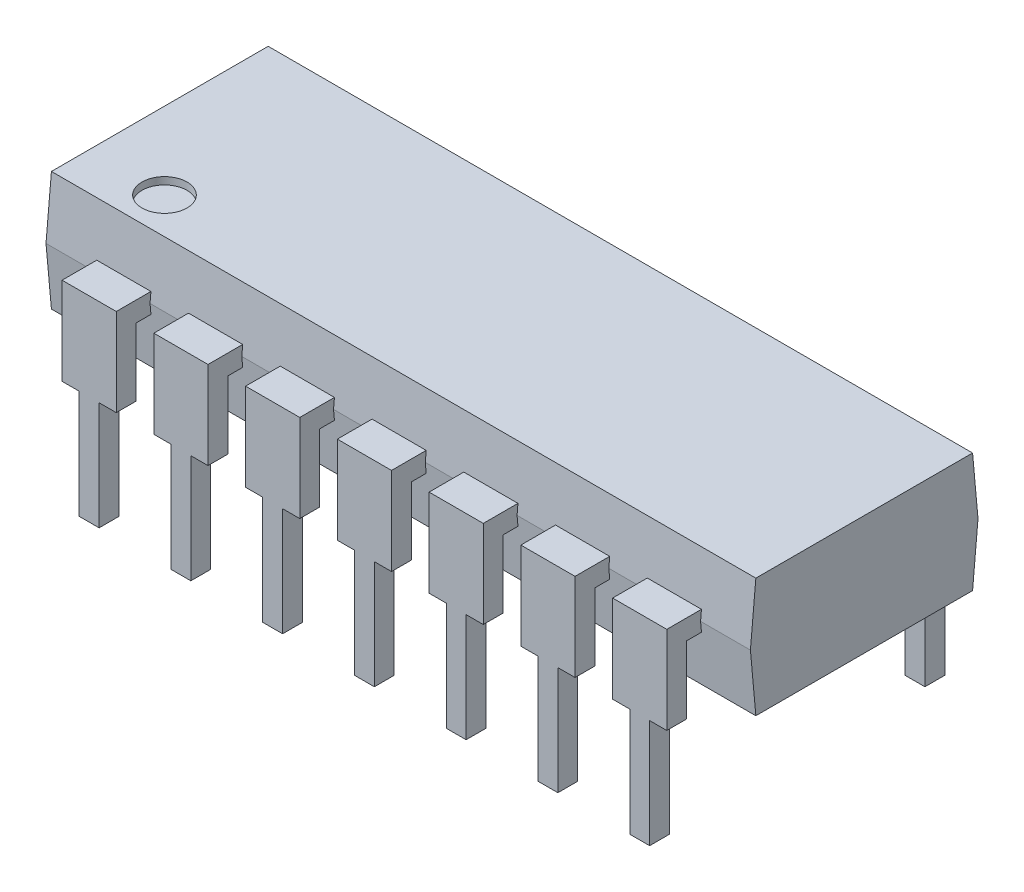
SolidWorks part; units mm, degrees
ref_plane "Front Plane" through (0, 0, 0) normal (0, 0, 1) x (1, 0, 0)
ref_plane "Top Plane" through (0, 0, 0) normal (0, 1, 0) x (1, 0, 0)
ref_plane "Right Plane" through (0, 0, 0) normal (1, 0, 0) x (0, 0, -1)
sketch "Sketch2" plane through (0, 0, 0) normal (1, 0, 0) x (0, 0, -1)
  line L0 (0, 0) -> (0, 3.3)
  line L1 (0, 3.3) -> (-3, 3.3)
  line L2 (-3, 3.3) -> (-3.15, 1.65)
  line L3 (-3.15, 1.65) -> (-3, 0)
  line L4 (-3, 0) -> (0, 0)
  line L5 (-3.15, 1.65) -> (0, 1.65) construction
  line L6 (-3, 3.3) -> (-3, 0) construction
  dimension "D1" = 3.3
  dimension "D2" = 3.15
  dimension "D3" = 3
extrude "Boss-Extrude1" add sketch "Sketch2" along normal blind 19.5
sketch "Sketch3" plane through (0, 0, 0) normal (0, 1, 0) x (1, 0, 0)
  line L0 (1.855, -3.535) -> (2.405, -4.085) construction
  line L1 (1.855, -4.085) -> (2.405, -4.085)
  line L2 (1.855, -4.085) -> (1.855, -3.535)
  line L3 (1.855, -3.535) -> (2.405, -3.535)
  line L4 (2.405, -4.085) -> (2.405, -3.535)
  line L5 (2.405, -3.535) -> (1.855, -4.085) construction
  point P4 (2.13, -3.81)
  dimension "D1" = 0.55
  dimension "D2" = 3.81
  dimension "D3" = 2.13
ref_plane "Plane1" through (0, 1.65, 0) normal (0, 1, 0) x (1, 0, 0)
sketch "Sketch5" plane through (0, 1.65, 0) normal (0, 1, 0) x (1, 0, 0)
  line L1 (1.38, -4.085) -> (2.88, -4.085)
  line L2 (1.38, -4.085) -> (1.38, -3)
  line L3 (1.38, -3) -> (2.88, -3)
  line L4 (2.88, -4.085) -> (2.88, -3)
  line L5 (19.5, -3) -> (0, -3) construction
  line L6 (1.855, -4.085) -> (2.405, -4.085) construction
  line L7 (1.38, -3.535) -> (2.88, -3.535)
  line L8 (1.855, -3.535) -> (2.405, -3.535) construction
  line L9 (1.38, -3.535) -> (9.144, -3.535) construction
  point P12 (2.13, -4.085)
  point P15 (2.13, -4.085)
  dimension "D1" = 1.5
extrude "Boss-Extrude2" add sketch "Sketch5" along normal mid plane 0.55 separate body contours L7 L2 L1 L4 | L2 L7 L4 L3 region at (2.13, 1.65, 3.81) region at (2.13, 1.65, 3.2675)
extrude "Boss-Extrude4" add sketch "Sketch5<3>" against normal blind 2.15 contours L7 L2 L1 L4 region at (2.13, 1.65, 3.81)
sketch "Sketch5<3>" plane through (0, 1.65, 0) normal (0, 1, 0) x (1, 0, 0) same geometry as "Sketch5"
extrude "Boss-Extrude5" add sketch "Sketch3" against normal blind 3.5
pattern_linear "LPattern1" count 7 spacing 2.54 along (1, 0, 0) of "Boss-Extrude2", "Boss-Extrude5", "Boss-Extrude4"
mirror "Mirror2" about plane through (0, 0, 0) normal (0, 0, 1) of "Boss-Extrude1"
mirror "Mirror3" about plane through (0, 0, 0) normal (0, 0, 1) of "LPattern1", "Boss-Extrude5", "Boss-Extrude4", "Boss-Extrude2"
sketch "Sketch6" plane through (0, 3.3, 0) normal (0, 1, 0) x (1, 0, 0)
  line L0 (2.13, -2) -> (2.13, -3.81) construction
  circle A0 centre (2.13, -2) radius 0.6237
  dimension "D1" = 2
extrude "Cut-Extrude1" cut sketch "Sketch6" against normal blind 0.2
ref_axis "Axis1" through (2.13, 0, 3.81) along (0, -1, 0)
